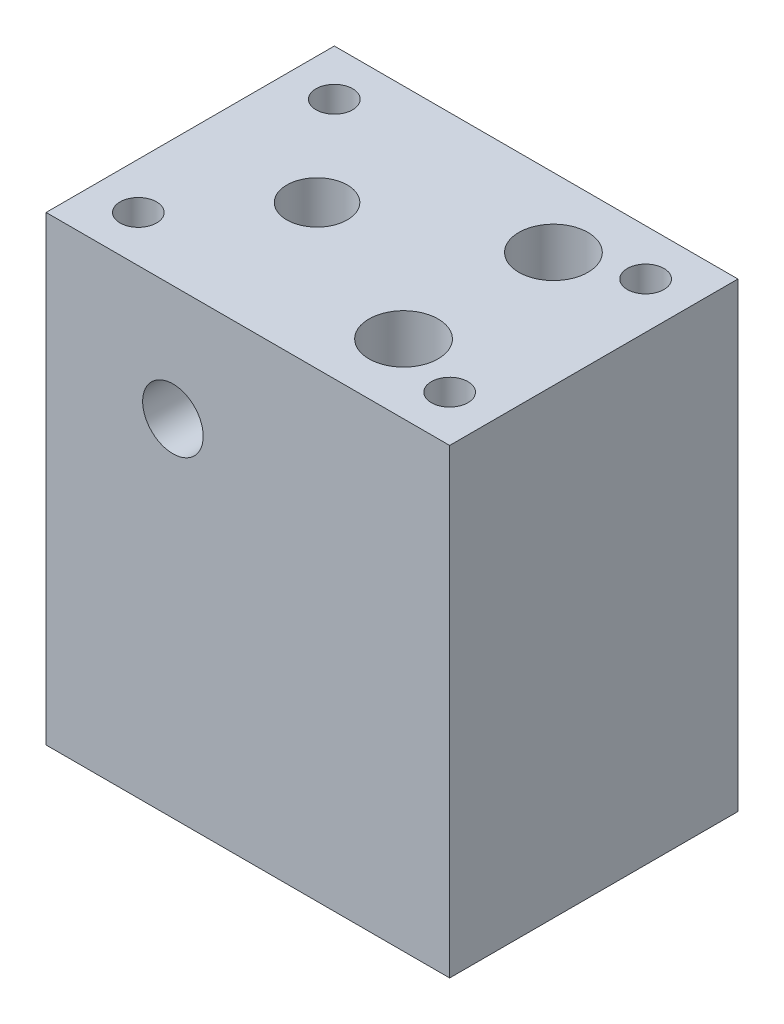
SolidWorks part; units mm, degrees
ref_plane "Front Plane" through (0, 0, 0) normal (0, 0, 1) x (1, 0, 0)
ref_plane "Top Plane" through (0, 0, 0) normal (0, 1, 0) x (1, 0, 0)
ref_plane "Right Plane" through (0, 0, 0) normal (1, 0, 0) x (0, 0, -1)
sketch "Sketch1" plane through (0, 0, 0) normal (0, 1, 0) x (1, 0, 0)
  line L1 (0, 0) -> (35, 0)
  line L2 (0, 0) -> (0, 25)
  line L3 (0, 25) -> (35, 25)
  line L4 (35, 0) -> (35, 25)
  dimension "D1" = 35
  dimension "D2" = 25
extrude "Boss-Extrude1" add sketch "Sketch1" along normal blind 40
sketch "Sketch2" plane through (0, 0, 0) normal (0, 1, 0) x (1, 0, 0)
  line L0 (0, 12.5) -> (35, 12.5) construction
  line L1 (0, 25) -> (0, 0) construction
  line L2 (35, 0) -> (35, 25) construction
  circle A0 centre (11, 12.5) radius 5.5
  point P9 (5.5, 12.5)
  dimension "D1" = 11
  dimension "D2" = 11
extrude "Cut-Extrude1" cut sketch "Sketch2" along normal blind 35
sketch "Sketch3" plane through (0, 40, 0) normal (0, 1, 0) x (1, 0, 0)
  line L0 (25, 25) -> (25, 0) construction
  line L1 (35, 25) -> (0, 25) construction
  line L2 (0, 0) -> (35, 0) construction
  line L3 (35, 12.5) -> (0, 12.5) construction
  line L4 (35, 0) -> (35, 25) construction
  line L5 (0, 25) -> (0, 0) construction
  circle A0 centre (25, 19) radius 3
  circle A1 centre (25, 6) radius 3
  dimension "D1" = 6
  dimension "D2" = 6
  dimension "D3" = 25
extrude "Cut-Extrude2" cut sketch "Sketch3" against normal blind 20 contours A1
extrude "Cut-Extrude5" cut sketch "Sketch3<4>" against normal blind 35 contours A0
sketch "Sketch3<4>" plane through (0, 40, 0) normal (0, 1, 0) x (1, 0, 0) same geometry as "Sketch3"
sketch "Sketch4" plane through (0, 0, 0) normal (0, 0, 1) x (1, 0, 0)
  line L0 (11, 40) -> (11, 0) construction
  line L1 (0, 40) -> (35, 40) construction
  line L2 (0, 0) -> (35, 0) construction
  line L3 (16.5, 40) -> (5.5, 40) construction
  line L4 (16.5, 40) -> (5.5, 40)
  circle A0 centre (11, 30) radius 2.625
  dimension "D1" = 5.25
  dimension "D2" = 10
extrude "Cut-Extrude3" cut sketch "Sketch4" against normal blind 10 contours A0
sketch "Sketch5" plane through (0, 40, 0) normal (0, 1, 0) x (1, 0, 0)
  line L0 (0, 12.5) -> (35, 12.5) construction
  line L1 (0, 25) -> (0, 0) construction
  line L2 (35, 0) -> (35, 25) construction
  line L3 (17.5, 0) -> (17.5, 25) construction
  line L4 (0, 0) -> (35, 0) construction
  line L5 (35, 25) -> (0, 25) construction
  circle A0 centre (4, 4) radius 1.5875
  circle A1 centre (4, 21) radius 1.5875
  circle A2 centre (31, 4) radius 1.5875
  circle A3 centre (31, 21) radius 1.5875
  dimension "D3" = 3.175
  dimension "D1" = 4
  dimension "D2" = 4
extrude "Cut-Extrude4" cut sketch "Sketch5" against normal blind 6.35
ref_plane "Plane1" through (0, 0, -12.5) normal (0, 0, -1) x (-1, 0, 0)
ref_plane "Plane2" through (17.5, 0, 0) normal (1, 0, 0) x (0, 0, -1)
sketch "Sketch6" plane through (0, 35, 0) normal (0, -1, 0) x (1, 0, 0)
  circle A0 centre (11, -12.5) radius 2.625
  dimension "D1" = 5.25
extrude "Cut-Extrude6" cut sketch "Sketch6" against normal through all
chamfer "Chamfer1" distance 4 angle 35 1 edges at (11, 35, -7) first distance on face at (11, 35, -15.125)
